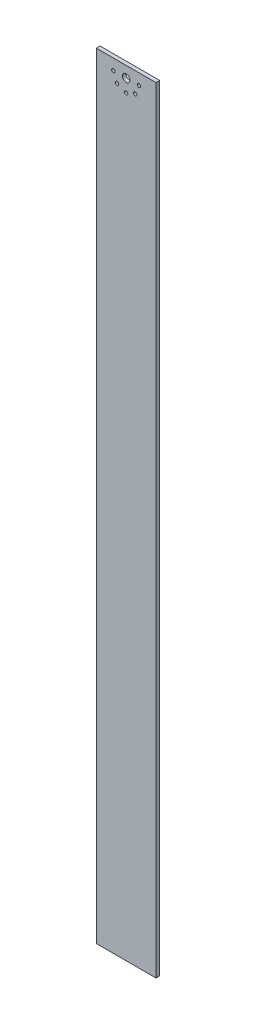
SolidWorks part; units mm, degrees
material "Teak"
ref_plane "Front Plane" through (0, 0, 0) normal (0, 0, 1) x (1, 0, 0)
ref_plane "Top Plane" through (0, 0, 0) normal (0, 1, 0) x (1, 0, 0)
ref_plane "Right Plane" through (0, 0, 0) normal (1, 0, 0) x (0, 0, -1)
sketch "Sketch1" plane through (0, 0, 0) normal (0, 0, 1) x (1, 0, 0)
  line L1 (-25.4, -330.2) -> (25.4, -330.2)
  line L2 (-25.4, -330.2) -> (-25.4, 330.2)
  line L3 (-25.4, 330.2) -> (25.4, 330.2)
  line L4 (25.4, -330.2) -> (25.4, 330.2)
  line L5 (-25.4, -330.2) -> (25.4, 330.2) construction
  line L6 (-25.4, 330.2) -> (25.4, -330.2) construction
  point P0 (0, 0)
  dimension "D1" = 50.8
  dimension "D2" = 660.4
extrude "Boss-Extrude1" add sketch "Sketch1" along normal blind 3.175
hole_wizard "M2.5 Clearance Hole1" positions "Sketch3" profile "Sketch2" hole size "M2.5" standard "ANSI Metric" end condition through all
sketch "Sketch3" plane through (0, 0, 3.175) normal (0, 0, 1) x (1, 0, 0)
  circle A0 centre (-11, 320.85) radius 1.025 construction
  circle A1 centre (-7.7782, 313.0718) radius 1.025 construction
  circle A2 centre (0, 309.85) radius 1.025 construction
  circle A3 centre (7.7782, 313.0718) radius 1.025 construction
  circle A4 centre (11, 320.85) radius 1.025 construction
  point P0 (-11, 320.85)
  point P3 (-7.7782, 313.0718)
  point P6 (0, 309.85)
  point P8 (7.7782, 313.0718)
  point P11 (11, 320.85)
sketch "Sketch2" plane through (-11, 320.85, 3.175) normal (1, 0, 0) x (0, -1, 0)
  line L0 (0, 0) -> (0, 3.175)
  line L1 (0, 3.175) -> (1.45, 3.175)
  line L2 (1.45, 3.175) -> (1.45, 0)
  line L5 (1.45, 0) -> (0, 0)
  line L11 (0, -6.35) -> (0, 107.95) construction
  dimension "Thru Hole Dia." = 2.9
  dimension "Thru Hole Depth" = 3.175
hole_wizard "1/4 (0.25) Diameter Hole1" positions "Sketch5" profile "Sketch4" hole size "1/4" standard "ANSI Inch" end condition through all
sketch "Sketch5" plane through (0, 0, 3.175) normal (0, 0, 1) x (1, 0, 0)
  arc A0 (-5, 320.85) -> (5, 320.85) centre (0, 320.85) ccw construction
  point P0 (0, 320.85)
sketch "Sketch4" plane through (0, 320.85, 3.175) normal (1, 0, 0) x (0, -1, 0)
  line L0 (0, 0) -> (0, 3.175)
  line L1 (0, 3.175) -> (3.175, 3.175)
  line L2 (3.175, 3.175) -> (3.175, 0)
  line L5 (3.175, 0) -> (0, 0)
  line L11 (0, -6.35) -> (0, 107.95) construction
  dimension "Thru Hole Dia." = 6.35
  dimension "Thru Hole Depth" = 3.175
